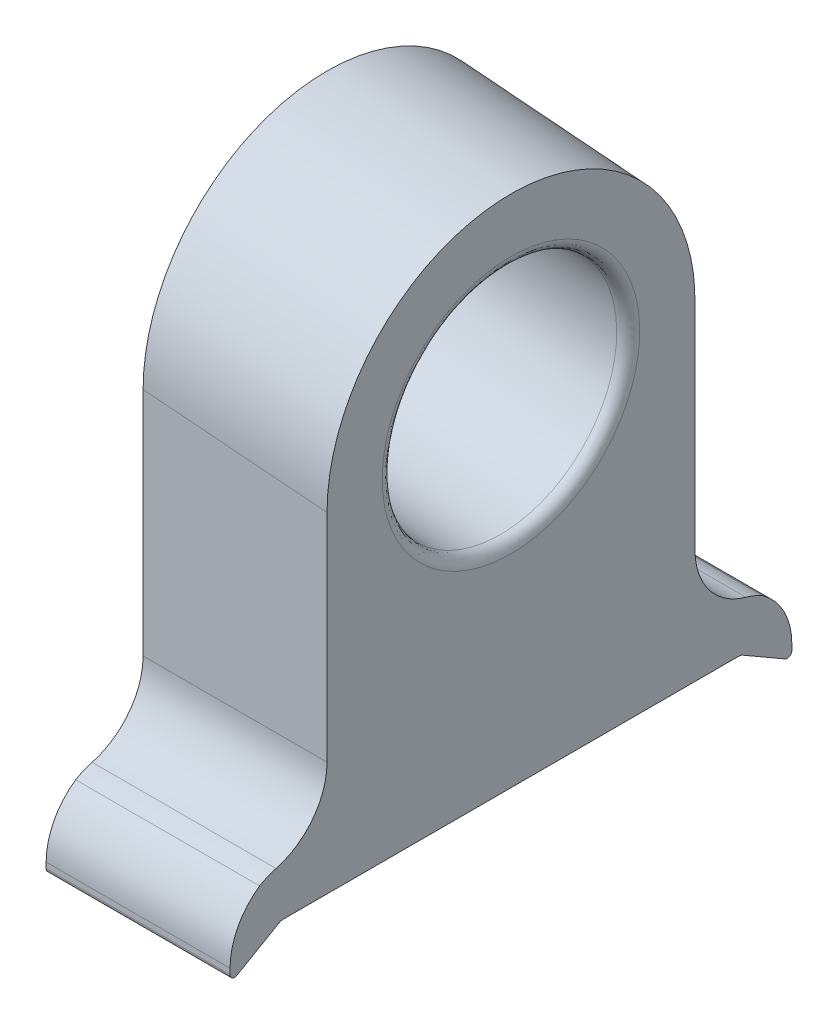
SolidWorks part; units mm, degrees
ref_plane "Front Plane" through (0, 0, 0) normal (0, 0, 1) x (1, 0, 0)
ref_plane "Top Plane" through (0, 0, 0) normal (0, 1, 0) x (1, 0, 0)
ref_plane "Right Plane" through (0, 0, 0) normal (1, 0, 0) x (0, 0, -1)
sketch "Sketch1" plane through (0, 0, 0) normal (0, 0, 1) x (1, 0, 0)
  line L0 (0, 0) -> (0, 51.366) construction
  line L1 (0, 0) -> (70.8704, -5.5776) construction
  dimension "D1" = 94.5
sketch "Sketch2" plane through (0, 0, 0) normal (0, 1, 0) x (1, 0, 0)
  line L0 (0, 0) -> (0, -8)
  line L1 (0, 0) -> (0, 8)
  line L2 (0, 8) -> (8, 8)
  line L3 (8, 8) -> (8, -8)
  line L4 (8, -8) -> (0, -8)
  dimension "D1" = 8
  dimension "D2" = 8
  dimension "D3" = 8
extrude "Boss-Extrude1" add sketch "Sketch2" along normal blind 25
sketch "Sketch3" plane through (0, 0, 0) normal (1, 0, 0) x (0, 0, -1)
  line L0 (0, 0) -> (0, 51.366) construction
  line L1 (-8, 0) -> (8, 0) construction
  circle A0 centre (0, 15) radius 5.1
  dimension "D1" = 10.2
  dimension "D2" = 15
extrude "Cut-Extrude1" cut sketch "Sketch3" along direction (0.9969, -0.0785, 0) on the side of the normal blind 25
sketch "Sketch4" plane through (0, 0, 0) normal (1, 0, 0) x (0, 0, -1)
  line L0 (-5.1, 15) -> (-8, 15) construction
  line L1 (-8, 25) -> (-8, 0) construction
  line L2 (5.1, 15) -> (8, 15) construction
  line L3 (8, 25) -> (8, 0) construction
  line L4 (8, 15) -> (9.8752, 15)
  line L5 (9.8752, 15) -> (9.8752, 26.3859)
  line L6 (9.8752, 26.3859) -> (-10.5058, 26.3859)
  line L7 (-10.5058, 26.3859) -> (-10.5058, 15)
  line L8 (-10.5058, 15) -> (-8, 15)
  arc A0 (8, 15) -> (-8, 15) centre (0, 15) ccw
extrude "Cut-Extrude2" cut sketch "Sketch4" along direction (0.9969, -0.0785, 0) on the side of the normal blind 25
fillet "Fillet1" radius 0.5 2 edges at (8, 13.4385, 5.0141) (0, 15, -5.1)
sketch "Sketch5" plane through (0, 0, 0) normal (1, 0, 0) x (0, 0, -1)
  line L0 (0, -4) -> (0, -8.2) construction
  line L1 (0, -4) -> (0, 0) construction
  line L2 (-10.5359, 2) -> (-21.899, -4.5605)
  line L4 (10, 0) -> (17.2732, -4.1992)
  line L6 (10.5359, 2) -> (21.899, -4.5605)
  line L7 (10, 0) -> (-10, 0)
  line L8 (-10, 0) -> (-17.2732, -4.1992)
  line L9 (10.5359, 2) -> (-10.5359, 2)
  line L11 (-16.2175, -1.2802) -> (16.2175, -1.2802)
  line L16 (-17.2732, -4.1992) -> (0, -10.8531)
  line L17 (0, -10.8531) -> (17.2732, -4.1992)
  line L18 (-21.899, -4.5605) -> (0, -12.9963) construction
  line L19 (0, -12.9963) -> (21.899, -4.5605) construction
  dimension "D1" = 4.2
  dimension "D2" = 4
  dimension "D3" = 10
  dimension "D4" = 2
  dimension "D5" = 150
extrude "Boss-Extrude3" add sketch "Sketch5" along normal blind 8 contours L2 L11 L8 L7 L4 L6 L9 region at (0, 0.6779, 0)
fillet "Fillet2" radius 0.4 2 edges at (4, 0, -10) (4, 0, 10)
sketch "Sketch6" plane through (0, 0, 0) normal (1, 0, 0) x (0, 0, -1)
  line L0 (-12.2175, -1.2802) -> (-12.2175, 1.7274)
  line L1 (-12.2175, 1.7274) -> (-17.377, 1.7274)
  line L2 (-17.377, 1.7274) -> (-17.377, -2.1027)
  line L3 (-17.377, -2.1027) -> (-12.2175, -2.1027)
  line L4 (-12.2175, -2.1027) -> (-12.2175, -1.2802)
  line L5 (12.2175, -1.2802) -> (12.2175, 2.7305)
  line L6 (12.2175, 2.7305) -> (17.3122, 2.7305)
  line L7 (17.3122, 2.7305) -> (17.3122, -3.6164)
  line L8 (17.3122, -3.6164) -> (12.2175, -3.6164)
  line L9 (12.2175, -3.6164) -> (12.2175, -1.2802)
extrude "Cut-Extrude3" cut sketch "Sketch6" along normal blind 8
fillet "Fillet4" radius 3 2 edges at (4, 2, 8) (4, 2, -8)
fillet "Fillet5" radius 3 2 edges at (4, 2, 10.5359) (4, 2, -10.5359)
fillet "Fillet6" radius 3 2 edges at (4, 1.0292, 12.2175) (4, 1.0292, -12.2175)
fillet "Fillet7" radius 0.2 2 edges at (4, -1.2802, 12.2175) (4, -1.2802, -12.2175)
